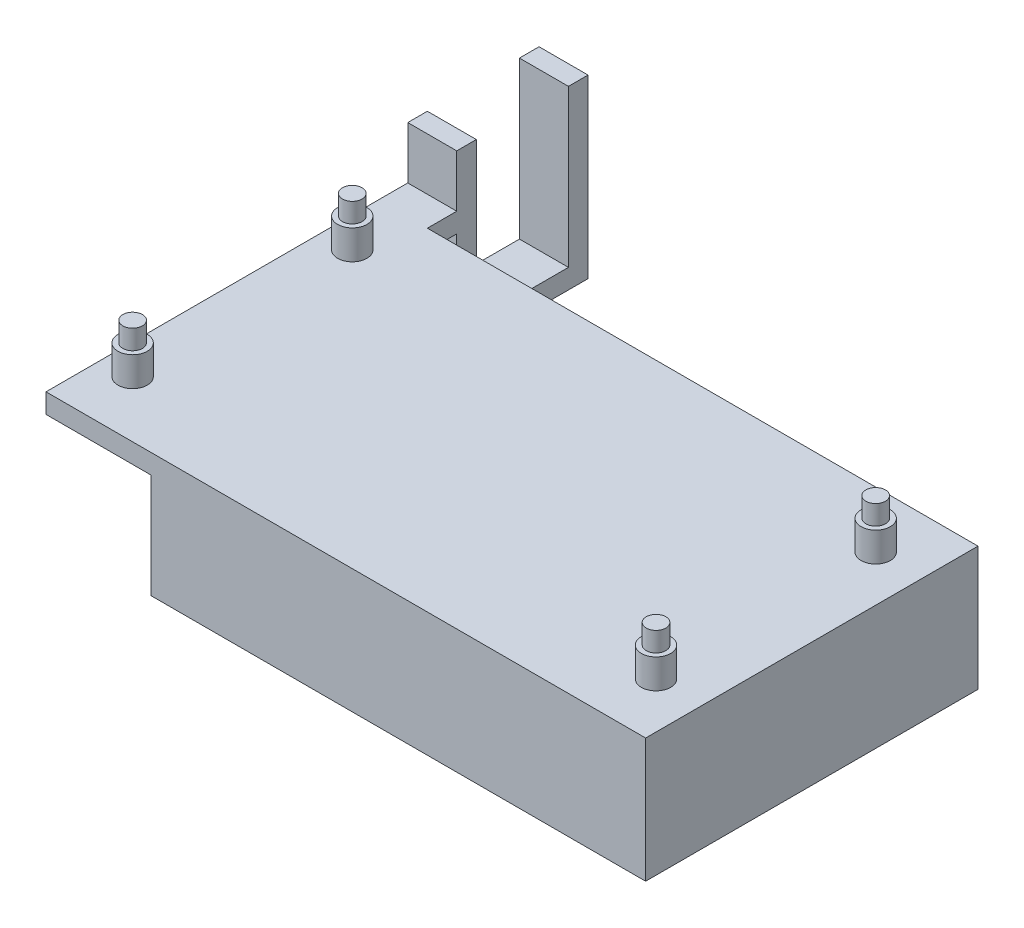
SolidWorks part; units mm, degrees
ref_plane "Front Plane" through (0, 0, 0) normal (0, 0, 1) x (1, 0, 0)
ref_plane "Top Plane" through (0, 0, 0) normal (0, 1, 0) x (1, 0, 0)
ref_plane "Right Plane" through (0, 0, 0) normal (1, 0, 0) x (0, 0, -1)
sketch "Sketch1" plane through (0, 0, 0) normal (1, 0, 0) x (0, 0, -1)
  line L1 (-19, 5.5) -> (19, 5.5)
  line L2 (-19, 5.5) -> (-19, -5.5)
  line L3 (-19, -5.5) -> (19, -5.5)
  line L4 (19, 5.5) -> (19, -5.5)
  line L5 (-19, 5.5) -> (19, -5.5) construction
  line L6 (-19, -5.5) -> (19, 5.5) construction
  line L7 (-21.54, 8.04) -> (21.54, 8.04)
  line L8 (-21.54, 8.04) -> (-21.54, -8.04)
  line L9 (-21.54, -8.04) -> (21.54, -8.04)
  line L10 (21.54, 8.04) -> (21.54, -8.04)
  line L11 (-21.54, 8.04) -> (21.54, -8.04) construction
  line L12 (-21.54, -8.04) -> (21.54, 8.04) construction
  point P0 (0, 0)
  point P6 (0, 0)
  dimension "D1" = 11
  dimension "D2" = 38
  dimension "D3" = 2.54
  dimension "D4" = 2.54
extrude "Boss-Extrude1" add sketch "Sketch1" against normal blind 57.785
extrude "Boss-Extrude2" add sketch "Sketch1<2>" along normal blind 2.54 contours L4 L1 L2 L3 | L10 L7 L8 L9 L1 L4 L3 L2 region at (0, 0, 0) region at (0, 7.5802, 0)
sketch "Sketch1<2>" plane through (0, 0, 0) normal (1, 0, 0) x (0, 0, -1) same geometry as "Sketch1"
sketch "Sketch3" plane through (0, 0, -21.54) normal (0, 0, -1) x (-1, 0, 0)
  line L0 (55.245, 2.921) -> (55.245, -5.5)
  line L1 (57.785, 5.5) -> (55.245, 5.5)
  line L2 (57.785, 5.5) -> (57.785, 2.96)
  line L4 (55.245, 5.5) -> (55.245, 2.921)
  line L5 (57.785, -5.5) -> (0, -5.5) construction
  line L6 (55.245, -5.5) -> (57.785, -5.5)
  line L7 (57.785, -5.5) -> (57.785, 2.96)
  dimension "D1" = 2.54
  dimension "D2" = 2.54
extrude "Cut-Extrude2" cut sketch "Sketch3" against normal blind 2.54
ref_plane "Plane1" through (-27.94, 0, 0) normal (1, 0, 0) x (0, 0, -1)
sketch "Sketch5" plane through (0, 8.04, 0) normal (0, 1, 0) x (1, 0, 0)
  line L0 (2.54, -21.54) -> (-69.596, -21.54)
  line L5 (2.54, 21.54) -> (-69.596, 21.54)
  line L7 (-69.596, 21.54) -> (-69.596, -21.54)
  line L9 (2.54, -16.383) -> (-69.596, -16.383) construction
  line L11 (2.54, 16.383) -> (2.54, -16.383)
  line L12 (2.54, 16.383) -> (-69.596, 16.383) construction
  line L13 (-67.4497, 16.383) -> (-67.4497, 14.2367) construction
  line L14 (-69.596, 14.2367) -> (-67.4497, 14.2367) construction
  line L16 (-8.844, 0) -> (8.844, 0) construction
  line L17 (2.54, 0) -> (-69.596, 0) construction
  line L20 (-33.528, -16.383) -> (-33.528, 16.383) construction
  line L23 (2.54, -16.383) -> (2.54, -21.54)
  circle A0 centre (-67.4497, 14.2367) radius 1.27
  circle A1 centre (-67.4497, -14.2367) radius 1.27
  circle A2 centre (0.3937, -14.2367) radius 1.27
  circle A3 centre (0.3937, 14.2367) radius 1.27
  circle A4 centre (-67.4497, 14.2367) radius 1.8966
  circle A5 centre (-67.4497, -14.2367) radius 1.8966
  circle A6 centre (0.3937, -14.2367) radius 1.8966
  circle A7 centre (0.3937, 14.2367) radius 1.8966
  line M14 (-57.785, 21.54) -> (-57.785, -21.54)
  line M16 (2.54, -21.54) -> (2.54, 21.54)
  dimension "D7" = 2.54
  dimension "D8" = 3.7932
  dimension "D1" = 72.136
  dimension "D2" = 32.766
  dimension "D3" = 5.157
extrude "Boss-Extrude8" add sketch "Sketch5" against normal blind 2.54 contours L23 M16 | L11 A6 A7 M16 | A6 A2 | A2 | M16 | A7 A3 | A3 | L5 L7 L0 A4 A5 M14 | A4 | A5 region at (-27.8683, 8.04, 0) region at (-63.5158, 8.04, 0) region at (0.3937, 8.04, 14.2367) region at (0.3937, 8.04, -14.2367) region at (-1.4493, 8.04, 14.2367) region at (-1.4493, 8.04, -14.2367)
extrude "Boss-Extrude9" add sketch "Sketch5<6>" along normal blind 6.35 contours A0 | A1 | A2 | A3 region at (-67.4497, 8.04, -14.2367) region at (-67.4497, 8.04, 14.2367)
sketch "Sketch5<6>" plane through (0, 8.04, 0) normal (0, 1, 0) x (1, 0, 0) same geometry as "Sketch5"
extrude "Boss-Extrude10" add sketch "Sketch5<8>" along normal blind 3.81 contours A4 A0 | A5 | A6 | A7 region at (-69.2927, 8.04, -14.2367)
sketch "Sketch5<8>" plane through (0, 8.04, 0) normal (0, 1, 0) x (1, 0, 0) same geometry as "Sketch5"
sketch "Sketch6" plane through (2.54, 0, 0) normal (1, 0, 0) x (0, 0, -1)
  line L4 (-21.54, 8.04) -> (-21.54, -8.04)
  line L5 (-21.54, -8.04) -> (21.54, -8.04)
  line L6 (21.54, -8.04) -> (21.54, 8.04)
  line L7 (21.54, 8.04) -> (-21.54, 8.04)
  line L8 (-21.54, 8.04) -> (-21.54, -8.04)
  line L9 (-21.54, -8.04) -> (21.54, -8.04)
  line L10 (21.54, -8.04) -> (21.54, 8.04)
  line L11 (21.54, 8.04) -> (-21.54, 8.04)
  dimension "D1" = 0
extrude "Boss-Extrude11" add sketch "Sketch6" along normal blind 3.81
sketch "Sketch7" plane through (-69.596, 0, 0) normal (-1, 0, 0) x (0, 0, 1)
  line L4 (21.54, 8.04) -> (-21.54, 8.04)
  line L5 (-21.54, 8.04) -> (-21.54, 5.5)
  line L6 (-21.54, 5.5) -> (21.54, 5.5)
  line L7 (21.54, 5.5) -> (21.54, 8.04)
  line L8 (21.54, 8.04) -> (-21.54, 8.04)
  line L9 (-21.54, 8.04) -> (-21.54, 5.5)
  line L10 (-21.54, 5.5) -> (21.54, 5.5)
  line L11 (21.54, 5.5) -> (21.54, 8.04)
  dimension "D1" = 0
extrude "Boss-Extrude12" add sketch "Sketch7" along normal blind 1.778
sketch "Sketch8" plane through (-71.374, 0, 0) normal (-1, 0, 0) x (0, 0, 1)
  line L0 (-21.54, 8.04) -> (-25.35, 8.04)
  line L1 (-25.35, 8.04) -> (-25.35, 14.82)
  line L3 (-25.35, -8.04) -> (-42.368, -8.04)
  line L4 (-42.368, -8.04) -> (-42.368, 14.82)
  line L5 (-21.54, 5.5) -> (-25.35, 5.5)
  line L6 (-27.89, 5.5) -> (-27.89, 14.82)
  line L9 (-39.828, -5.5) -> (-39.828, 14.82)
  line L10 (-21.54, 8.04) -> (-21.54, 5.5)
  line L12 (-39.828, 14.82) -> (-42.368, 14.82)
  line L13 (-27.89, 14.82) -> (-25.35, 14.82)
  line L14 (-27.89, 5.5) -> (-27.89, -5.5)
  line L15 (-25.35, 5.5) -> (-25.35, -5.5)
  line L16 (-27.89, -5.5) -> (-39.828, -5.5)
  line L17 (-25.35, -5.5) -> (-25.35, -8.04)
  line L18 (-25.35, 8.04) -> (-25.35, 5.5)
  line L19 (-27.89, -5.5) -> (-27.89, -8.04)
  line L20 (-39.828, -5.5) -> (-39.828, -8.04)
  line M15 (-21.54, 8.04) -> (-21.54, 5.5)
  dimension "D1" = 2.54
  dimension "D2" = 22.86
  dimension "D3" = 2.54
  dimension "D4" = 6.35
  dimension "D5" = 22.86
  dimension "D6" = 11.938
extrude "Boss-Extrude15" add sketch "Sketch8" against normal blind 6.35 contours L0 L18 L5 M15 region at (-71.374, 6.77, -23.445)
extrude "Boss-Extrude16" add sketch "Sketch8<5>" against normal blind 6.35 contours L14 L19 L3 L17 L15 L18 L1 L13 L6 | L20 L9 L12 L4 L3 | L16 L20 L3 L19 region at (-71.374, 3.39, -26.62) region at (-71.374, -6.77, -33.859) region at (-71.374, 3.39, -41.098)
sketch "Sketch8<5>" plane through (-71.374, 0, 0) normal (-1, 0, 0) x (0, 0, 1) same geometry as "Sketch8"
